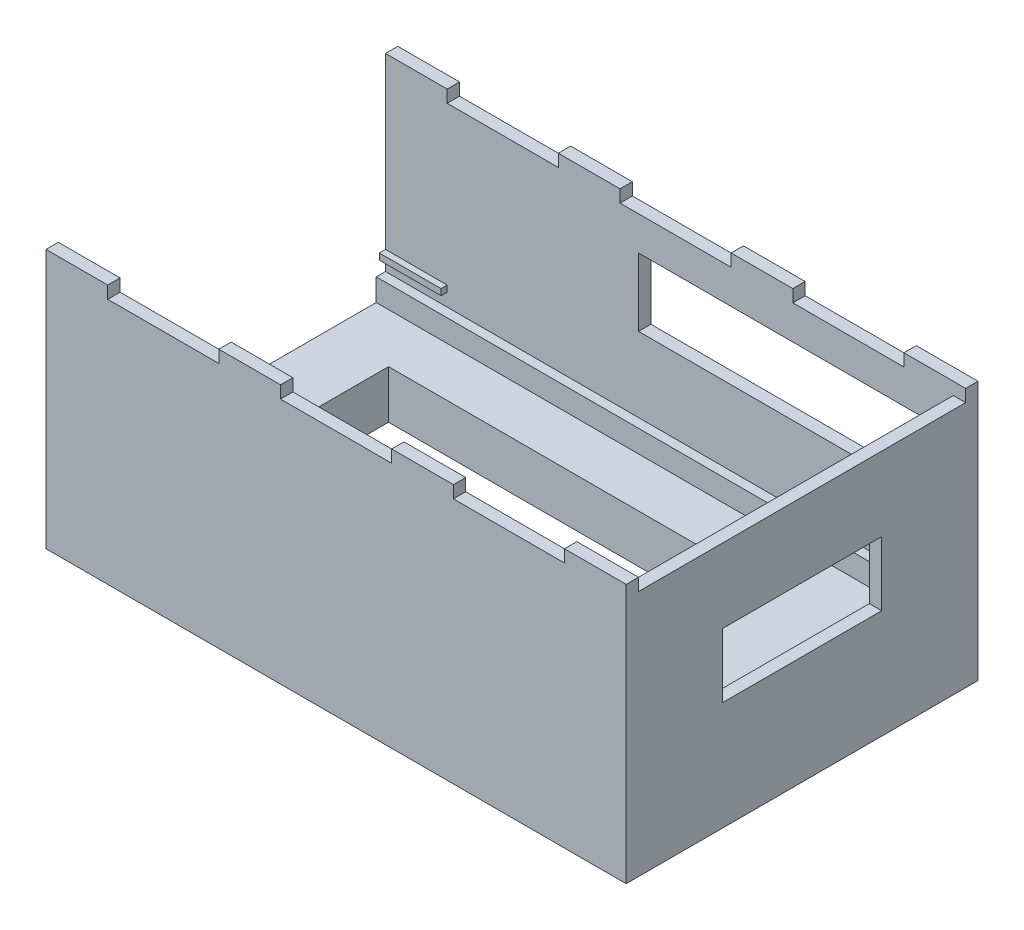
SolidWorks part; units mm, degrees
ref_plane "Front Plane" through (0, 0, 0) normal (0, 0, 1) x (1, 0, 0)
ref_plane "Top Plane" through (0, 0, 0) normal (0, 1, 0) x (1, 0, 0)
ref_plane "Right Plane" through (0, 0, 0) normal (1, 0, 0) x (0, 0, -1)
sketch "Sketch1" plane through (0, 0, 0) normal (0, 1, 0) x (1, 0, 0)
  line L1 (-30.298, 32.6459) -> (63.702, 32.6459)
  line L2 (-30.298, 32.6459) -> (-30.298, -24.3541)
  line L3 (-30.298, -24.3541) -> (63.702, -24.3541)
  line L4 (63.702, 32.6459) -> (63.702, -24.3541)
  dimension "D1" = 94
  dimension "D2" = 57
extrude "Boss-Extrude1" add sketch "Sketch1" along normal blind 10
sketch "Sketch2" plane through (0, 10, 0) normal (0, 1, 0) x (1, 0, 0)
  line L0 (-30.298, 32.6459) -> (63.702, 32.6459)
  line L1 (63.702, 32.6459) -> (63.702, -24.3541)
  line L2 (63.702, -24.3541) -> (-30.298, -24.3541)
  line L3 (-30.298, -24.3541) -> (-30.298, -22.3541)
  line L4 (-30.298, 32.6459) -> (-30.298, -24.3541) construction
  line L5 (-30.298, -22.3541) -> (61.702, -22.3541)
  line L6 (61.702, -22.3541) -> (61.702, 30.6459)
  line L7 (61.702, 30.6459) -> (-30.298, 30.6459)
  line L8 (-30.298, 30.6459) -> (-30.298, 32.6459)
  dimension "D1" = 2
  dimension "D2" = 2
  dimension "D3" = 2
extrude "Boss-Extrude2" add sketch "Sketch2" along normal blind 30
sketch "Sketch3" plane through (-30.298, 0, 0) normal (-1, 0, 0) x (0, 0, 1)
  line L0 (-30.6459, 40) -> (-30.6459, 10) construction
  line L1 (-30.6459, 10) -> (-29.1459, 10)
  line L2 (-30.6459, 10) -> (-30.6459, 11.4)
  line L3 (-30.6459, 11.4) -> (-29.1459, 11.4)
  line L4 (-29.1459, 10) -> (-29.1459, 11.4)
  line L5 (22.3541, 10) -> (20.8541, 10)
  line L6 (22.3541, 10) -> (22.3541, 11.4)
  line L7 (22.3541, 11.4) -> (20.8541, 11.4)
  line L8 (20.8541, 10) -> (20.8541, 11.4)
  line L9 (-30.6459, 14.5) -> (-29.6459, 14.5)
  line L10 (-30.6459, 14.5) -> (-30.6459, 13.5)
  line L11 (-30.6459, 13.5) -> (-29.6459, 13.5)
  line L12 (-29.6459, 14.5) -> (-29.6459, 13.5)
  line L13 (22.3541, 40) -> (22.3541, 10) construction
  line L14 (22.3541, 13.5) -> (21.3541, 13.5)
  line L15 (22.3541, 13.5) -> (22.3541, 14.5)
  line L16 (22.3541, 14.5) -> (21.3541, 14.5)
  line L17 (21.3541, 13.5) -> (21.3541, 14.5)
  dimension "D1" = 1.5
  dimension "D2" = 1.4
  dimension "D3" = 1.5
  dimension "D4" = 1.4
  dimension "D5" = 2.1
  dimension "D6" = 2.1
  dimension "D8" = 1
  dimension "D9" = 1
  dimension "D10" = 1
  dimension "D11" = 1
extrude "Boss-Extrude3" add sketch "Sketch3" against normal up to surface (92 mm away) contours L1 L4 L3 L2 | L5 L8 L7 L6 | L17 L16 L15 L14 up to face at (61.702, 25, -4.1459)
extrude "Boss-Extrude4" add sketch "Sketch3<3>" against normal blind 10 contours L12 L11 L10 L9
sketch "Sketch3<3>" plane through (-30.298, 0, 0) normal (-1, 0, 0) x (0, 0, 1) same geometry as "Sketch3"
sketch "Sketch4" plane through (0, 0, -32.6459) normal (0, 0, -1) x (-1, 0, 0)
  line L0 (-63.702, 40) -> (-63.702, 0) construction
  line L1 (-56.702, 34.5) -> (-10.702, 34.5)
  line L2 (-56.702, 34.5) -> (-56.702, 23.5)
  line L3 (-56.702, 23.5) -> (-10.702, 23.5)
  line L4 (-10.702, 34.5) -> (-10.702, 23.5)
  point P4 (-56.702, 29)
  dimension "D1" = 7
  dimension "D2" = 46
  dimension "D3" = 11
  dimension "D4" = 9
extrude "Cut-Extrude1" cut sketch "Sketch4" against normal blind 10
sketch "Sketch5" plane through (63.702, 0, 0) normal (1, 0, 0) x (0, 0, -1)
  line L1 (-8.7541, 28) -> (17.0459, 28)
  line L2 (-8.7541, 28) -> (-8.7541, 17.6)
  line L3 (-8.7541, 17.6) -> (17.0459, 17.6)
  line L4 (17.0459, 28) -> (17.0459, 17.6)
  line L5 (-24.3541, 40) -> (32.6459, 40) construction
  line L6 (4.1459, 40) -> (4.1459, 0) construction
  line L8 (-24.3541, 0) -> (32.6459, 0) construction
  point P10 (4.1459, 28)
  dimension "D1" = 0
  dimension "D2" = 25.8
  dimension "D3" = 12
  dimension "D4" = 10.4
extrude "Cut-Extrude2" cut sketch "Sketch5" against normal up to surface (2 mm away) up to face at (61.702, 16.8, 4.5207)
ref_plane "Plane5" through (0, 33, 0) normal (0, 1, 0) x (1, 0, 0)
sketch "Sketch7" plane through (0, 33, 0) normal (0, 1, 0) x (1, 0, 0)
  line L0 (61.702, -22.3541) -> (-30.298, -22.3541) construction
  line L1 (10.702, -22.3541) -> (61.702, -22.3541)
  line L2 (10.702, -22.3541) -> (10.702, -20.3541)
  line L3 (10.702, -20.3541) -> (59.702, -20.3541)
  line L4 (61.702, -22.3541) -> (61.702, -20.3541)
  line L5 (61.702, 29.1459) -> (61.702, -20.8541) construction
  line L6 (61.702, 30.6459) -> (61.702, -22.3541) construction
  line L8 (59.702, -20.3541) -> (59.702, 15.6459)
  line L9 (59.702, 15.6459) -> (61.702, 15.6459)
  line L10 (61.702, -20.3541) -> (61.702, 15.6459)
  dimension "D1" = 51
  dimension "D2" = 2
  dimension "D3" = 38
  dimension "D4" = 2
extrude "Boss-Extrude5" add sketch "Sketch7" against normal blind 2 contours L3 L8 L9 L10 L4 L1 L2
fillet "Fillet1" radius 1.5 2 edges at (59.702, 31, 2.3541) (35.202, 31, 20.3541) conic radius 3
ref_plane "Plane6" through (0, 34.8, 0) normal (0, 1, 0) x (1, 0, 0)
sketch "Sketch8" plane through (0, 34.8, 0) normal (0, 1, 0) x (1, 0, 0)
  line L1 (10.702, -20.3541) -> (59.702, -20.3541)
  line L2 (10.702, -20.3541) -> (10.702, -22.3541)
  line L3 (10.702, -22.3541) -> (61.702, -22.3541)
  line L4 (61.702, -20.3541) -> (61.702, -22.3541)
  line L5 (61.702, -22.3541) -> (59.702, -22.3541)
  line L6 (61.702, -22.3541) -> (61.702, 15.6459)
  line L7 (61.702, 15.6459) -> (59.702, 15.6459)
  line L8 (59.702, -20.3541) -> (59.702, 15.6459)
extrude "Boss-Extrude6" add sketch "Sketch8" along normal blind 1 contours L6 L7 L8 L1 L2 L3
sketch "Sketch9" plane through (0, 40, 0) normal (0, 1, 0) x (1, 0, 0)
  line L0 (-30.298, 30.6459) -> (61.702, 30.6459) construction
  line L1 (-30.298, 32.6459) -> (-20.298, 32.6459)
  line L2 (-30.298, 32.6459) -> (-30.298, 30.6459)
  line L3 (-30.298, 30.6459) -> (-20.298, 30.6459)
  line L4 (-20.298, 32.6459) -> (-20.298, 30.6459)
  line L5 (61.702, 30.6459) -> (-30.298, 30.6459) construction
  line L6 (-2.298, 30.6459) -> (7.702, 30.6459)
  line L7 (-2.298, 30.6459) -> (-2.298, 32.6459)
  line L8 (-2.298, 32.6459) -> (7.702, 32.6459)
  line L9 (7.702, 30.6459) -> (7.702, 32.6459)
  line L10 (63.702, 32.6459) -> (-30.298, 32.6459) construction
  line L11 (61.702, -22.3541) -> (-30.298, -22.3541) construction
  line L12 (25.702, 30.6459) -> (35.702, 30.6459)
  line L13 (25.702, 30.6459) -> (25.702, 32.6459)
  line L14 (25.702, 32.6459) -> (35.702, 32.6459)
  line L15 (35.702, 30.6459) -> (35.702, 32.6459)
  line L16 (53.702, 30.6459) -> (63.702, 30.6459)
  line L17 (53.702, 30.6459) -> (53.702, 32.6459)
  line L18 (53.702, 32.6459) -> (63.702, 32.6459)
  line L19 (63.702, 30.6459) -> (63.702, 32.6459)
  line L20 (-30.298, -24.3541) -> (-20.298, -24.3541)
  line L21 (-30.298, -24.3541) -> (-30.298, -22.3541)
  line L22 (-30.298, -22.3541) -> (-20.298, -22.3541)
  line L23 (-20.298, -24.3541) -> (-20.298, -22.3541)
  line L24 (-30.298, -24.3541) -> (63.702, -24.3541) construction
  line L25 (-2.298, -24.3541) -> (7.702, -24.3541)
  line L26 (-2.298, -24.3541) -> (-2.298, -22.3541)
  line L27 (-2.298, -22.3541) -> (7.702, -22.3541)
  line L28 (7.702, -24.3541) -> (7.702, -22.3541)
  line L29 (10.702, -22.3541) -> (61.702, -22.3541) construction
  line L30 (25.702, -24.3541) -> (35.702, -24.3541)
  line L31 (25.702, -24.3541) -> (25.702, -22.3541)
  line L32 (25.702, -22.3541) -> (35.702, -22.3541)
  line L33 (35.702, -24.3541) -> (35.702, -22.3541)
  line L35 (63.702, -24.3541) -> (53.702, -24.3541)
  line L36 (63.702, -24.3541) -> (63.702, -22.3541)
  line L37 (63.702, -22.3541) -> (53.702, -22.3541)
  line L38 (53.702, -24.3541) -> (53.702, -22.3541)
  dimension "D1" = 10
  dimension "D2" = 10
  dimension "D3" = 18
  dimension "D4" = 18
  dimension "D5" = 10
  dimension "D6" = 18
  dimension "D7" = 18
  dimension "D8" = 18
  dimension "D9" = 18
  dimension "D10" = 10
  dimension "D11" = 10
  dimension "D12" = 10
extrude "Boss-Extrude7" add sketch "Sketch9" along normal blind 2
sketch "Sketch10" plane through (0, 10, 0) normal (0, 1, 0) x (1, 0, 0)
  line L0 (-30.298, 4.1459) -> (61.702, 4.1459) construction
  line L1 (-20.298, 21.1459) -> (31.702, 21.1459)
  line L2 (-20.298, 21.1459) -> (-20.298, -12.8541)
  line L3 (-20.298, -12.8541) -> (31.702, -12.8541)
  line L4 (31.702, 21.1459) -> (31.702, -12.8541)
  line L5 (-30.298, 29.1459) -> (-30.298, -20.8541) construction
  line L6 (61.702, 30.6459) -> (61.702, -22.3541) construction
  point P10 (31.702, 4.1459)
  dimension "D1" = 34
  dimension "D2" = 0
  dimension "D3" = 52
  dimension "D4" = 10
extrude "Cut-Extrude3" cut sketch "Sketch10" against normal through all and the other way through all
sketch "Sketch11" plane through (0, 10, 0) normal (0, 1, 0) x (1, 0, 0)
  line L1 (61.702, 29.1459) -> (-30.298, 29.1459)
  line L2 (61.702, 29.1459) -> (61.702, -20.8541)
  line L3 (61.702, -20.8541) -> (-30.298, -20.8541)
  line L4 (-30.298, 29.1459) -> (-30.298, -20.8541)
extrude "Cut-Extrude4" cut sketch "Sketch11" against normal blind 2.2
